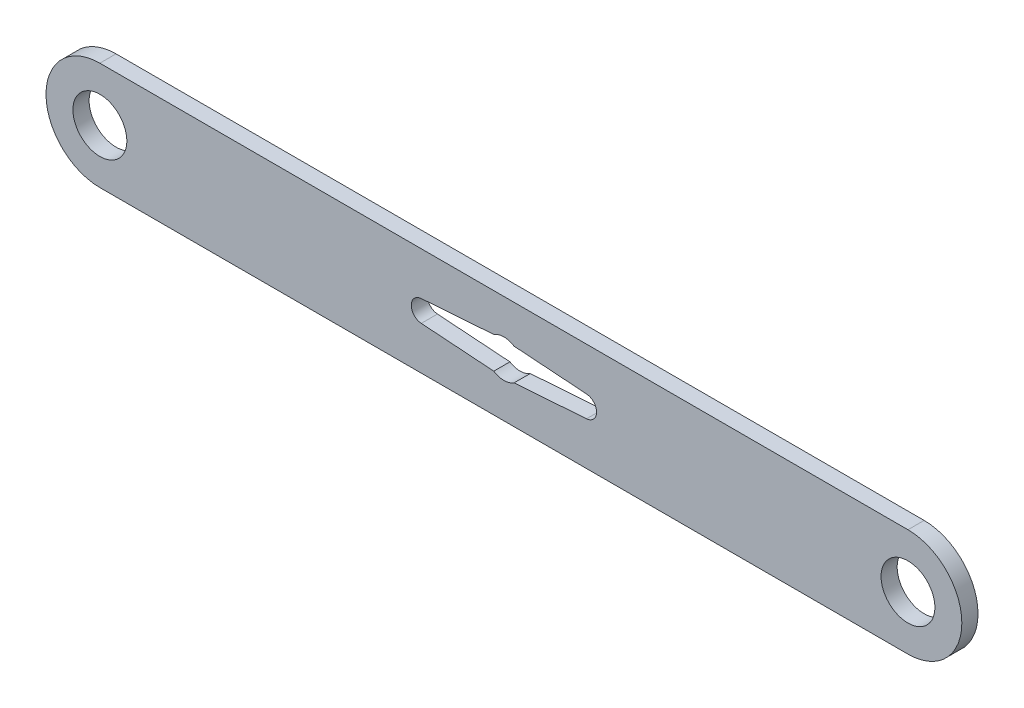
SolidWorks part; units mm, degrees
material "Acrylic (Medium-high impact)"
ref_plane "Front Plane" through (0, 0, 0) normal (0, 0, 1) x (1, 0, 0)
ref_plane "Top Plane" through (0, 0, 0) normal (0, 1, 0) x (1, 0, 0)
ref_plane "Right Plane" through (0, 0, 0) normal (1, 0, 0) x (0, 0, -1)
sketch "Sketch1" plane through (0, 0, 0) normal (0, 0, 1) x (1, 0, 0)
  line L0 (75, 0) -> (-75, 0) construction
  line L1 (75, -10) -> (-75, -10)
  line L2 (75, 10) -> (-75, 10)
  line L3 (-1.8835, 2.95) -> (-15.3416, 1.995)
  line L5 (0, 3.5) -> (0, -3.5) construction
  line L11 (-1.8835, -2.95) -> (-15.3416, -1.995)
  line L12 (1.8835, -2.95) -> (15.3416, -1.995)
  line L13 (1.8835, 2.95) -> (15.3416, 1.995)
  arc A0 (75, -10) -> (75, 10) centre (75, 0) ccw
  arc A1 (-75, 10) -> (-75, -10) centre (-75, 0) ccw
  circle A2 centre (75, 0) radius 5
  circle A3 centre (-75, 0) radius 5
  arc A16 (-1.8835, -2.95) -> (1.8835, -2.95) centre (0, 0) ccw
  arc A17 (-15.3416, 1.995) -> (-15.3416, -1.995) centre (-15.2, 0) ccw
  arc A18 (15.3416, 1.995) -> (15.3416, -1.995) centre (15.2, 0) cw
  arc A19 (-1.8835, 2.95) -> (-3.5, 0) centre (0, 0) ccw construction
  arc A20 (-3.5, 0) -> (-1.8835, -2.95) centre (0, 0) ccw construction
  arc A21 (1.8835, -2.95) -> (3.5, 0) centre (0, 0) ccw construction
  arc A22 (1.8835, 2.95) -> (-1.8835, 2.95) centre (0, 0) ccw
  arc A23 (3.5, 0) -> (1.8835, 2.95) centre (0, 0) ccw construction
  point P2 (0, 0)
  point P25 (-17.2, 0)
  dimension "D2" = 10
  dimension "D8" = 2
  dimension "D4" = 10
  dimension "D6" = 5.9
  dimension "D7" = 17.2
  dimension "D5" = 7
  dimension "D1" = 150
  dimension "D3" = 20
extrude "Boss-Extrude1" add sketch "Sketch1" along normal blind 3
